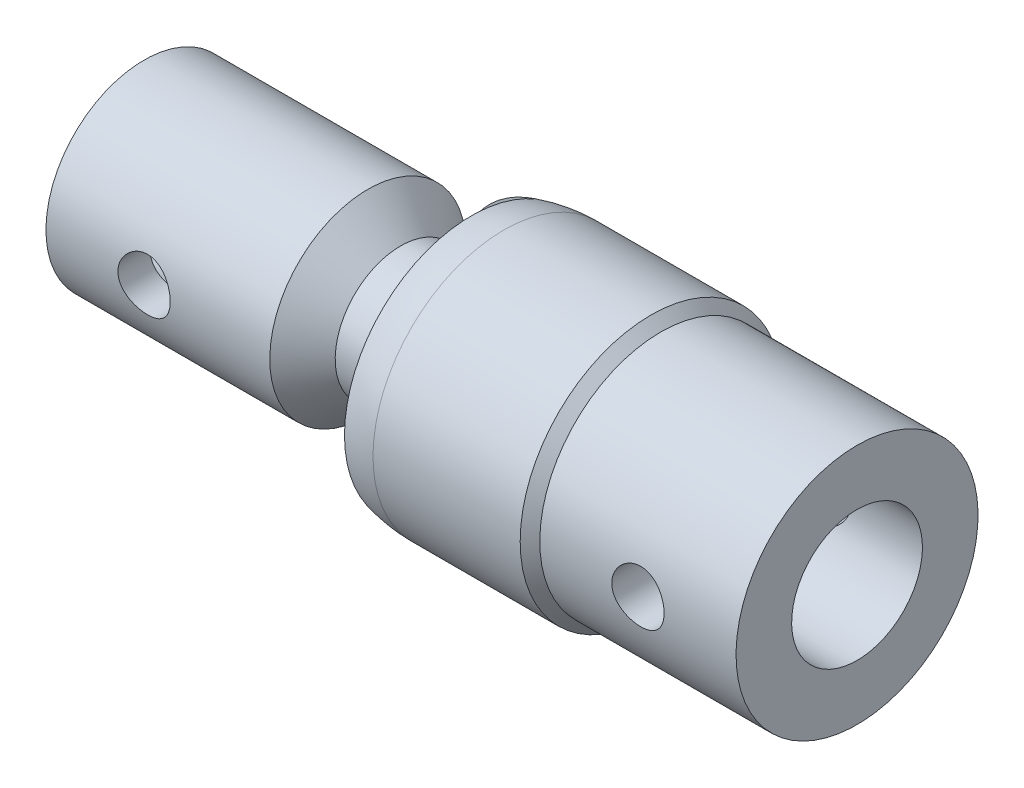
SolidWorks part; units mm, degrees
ref_plane "Front Plane" through (0, 0, 0) normal (0, 0, 1) x (1, 0, 0)
ref_plane "Top Plane" through (0, 0, 0) normal (0, 1, 0) x (1, 0, 0)
ref_plane "Right Plane" through (0, 0, 0) normal (1, 0, 0) x (0, 0, -1)
sketch "Sketch0" plane through (0, 0, 0) normal (0, 0, 1) x (1, 0, 0)
  line L0 (-43.6575, 0) -> (42.8625, 0) construction
  line L1 (42.8625, 7.9375) -> (19.05, 7.9375)
  line L2 (19.05, 7.9375) -> (19.05, -7.9375)
  line L3 (19.05, -7.9375) -> (42.8625, -7.9375)
  line L4 (42.8625, 14.6844) -> (42.8625, -14.6844) construction
  line L5 (-43.6575, 7.9375) -> (-19.845, 7.9375)
  line L6 (-19.845, 7.9375) -> (-19.845, -7.9375)
  line L7 (-19.845, -7.9375) -> (-43.6575, -7.9375)
  line L8 (-43.6575, 11.9062) -> (-43.6575, -11.9062) construction
  line L9 (0, 15.875) -> (0, -15.875) construction
  line L10 (0, 15.875) -> (0, -15.875) construction
  line L11 (42.8625, -14.6844) -> (19.05, -14.6844)
  line L12 (19.05, -14.6844) -> (17.8594, -15.875)
  line L13 (17.8594, -15.875) -> (0, -15.875)
  line L14 (-43.6575, -11.9062) -> (-16.4975, -11.9062)
  line L15 (-16.4975, -11.9062) -> (-12.5288, -7.9375)
  line L16 (-12.5288, -7.9375) -> (0, -7.9375)
  line L17 (5.6127, 5.6127) -> (11.2253, 11.2253) construction
  line L18 (-19.845, -7.9375) -> (-13.7482, -7.9375) construction
  circle A0 centre (0, 0) radius 15.875 construction
  circle A1 centre (0, 0) radius 7.9375 construction
  circle A2 centre (0, 0) radius 11.9062 construction
  point P5 (19.05, 0)
  point P30 (8.419, 8.419)
  dimension "D1" = 45
  dimension "F" = 43.6575
  dimension "G" = 42.8625
  dimension "A" = 15.875
  dimension "D2" = 45
  dimension "H" = 23.8125
  dimension "E" = 29.3687
  dimension "D" = 23.8125
  dimension "C" = 31.75
  dimension "D3" = 45
  dimension "D4" = 6.0969
  dimension "D5" = 7.3162
sketch "Sketch1" plane through (0, 0, 0) normal (0, 0, 1) x (1, 0, 0)
  line L0 (-12.5288, -7.9375) -> (0, -7.9375) construction
  line L1 (-16.4975, -11.9062) -> (-12.5288, -7.9375) construction
  line L2 (-43.6575, -11.9062) -> (-16.4975, -11.9062) construction
  line L3 (-19.845, -7.9375) -> (-43.6575, -7.9375) construction
  line L4 (-19.845, 7.9375) -> (-19.845, -7.9375) construction
  line L5 (-12.5288, -7.9375) -> (-8.8744, -7.9375)
  line L6 (-16.4975, -11.9062) -> (-12.5288, -7.9375)
  line L7 (-43.6575, -11.9062) -> (-16.4975, -11.9062)
  line L8 (-19.845, -7.9375) -> (-43.6575, -7.9375)
  line L9 (-19.845, 0) -> (-19.845, -7.9375)
  line L10 (-19.845, 0) -> (11.9062, 0) construction
  line L12 (-43.6575, -7.9375) -> (-43.6575, -11.9062)
  line L13 (-43.6575, 0) -> (42.8625, 0) construction
  line L14 (-19.845, 0) -> (11.9062, 0)
  arc A0 (-8.8744, -7.9375) -> (11.9062, 0) centre (0, 0) ccw
  circle A1 centre (0, 0) radius 11.9062 construction
revolve "Revolve1" add sketch "Sketch1" angle 360 about L10
sketch "Sketch2" plane through (0, 0, 0) normal (0, 0, 1) x (1, 0, 0)
  line L0 (19.05, 7.9375) -> (19.05, -7.9375) construction
  line L1 (19.05, -7.9375) -> (42.8625, -7.9375) construction
  line L2 (42.8625, -14.6844) -> (19.05, -14.6844) construction
  line L3 (19.05, -14.6844) -> (17.8594, -15.875) construction
  line L4 (17.8594, -15.875) -> (0, -15.875) construction
  line L5 (19.05, 0) -> (19.05, -7.9375)
  line L6 (19.05, -7.9375) -> (42.8625, -7.9375)
  line L7 (42.8625, -14.6844) -> (19.05, -14.6844)
  line L8 (19.05, -14.6844) -> (17.8594, -15.875)
  line L9 (17.8594, -15.875) -> (0, -15.875)
  line L10 (42.8625, -7.9375) -> (42.8625, -14.6844)
  line L11 (19.05, 0) -> (-15.875, 0) construction
  line L13 (-43.6575, 0) -> (42.8625, 0) construction
  line L14 (19.05, 0) -> (-15.875, 0)
  circle A0 centre (0, 0) radius 15.875 construction
  arc A1 (-15.875, 0) -> (0, -15.875) centre (0, 0) ccw
revolve "Revolve2" add sketch "Sketch2" angle 360 about L11
sketch "Sketch3" plane through (0, 0, 0) normal (0, 0, 1) x (1, 0, 0)
  line L0 (0, 0) -> (-7.9375, 0) construction
  line L1 (-43.6575, 0) -> (42.8625, 0) construction
  line L2 (-3.9688, 15.875) -> (-3.9687, -15.875)
  line L3 (-3.9688, 15.875) -> (-19.845, 15.875)
  line L4 (-3.9687, -15.875) -> (-19.845, -15.875)
  line L5 (-19.845, 15.875) -> (-19.845, -15.875)
  line L6 (-19.845, 7.9375) -> (-19.845, -7.9375) construction
  circle A0 centre (0, 0) radius 7.9375 construction
  point P9 (-3.9688, 0)
extrude "Cut-Extrude1" cut sketch "Sketch3" along normal through all and the other way blind 7.9375
sketch "Sketch5" plane through (0, 0, 0) normal (0, 0, 1) x (1, 0, 0)
  line L0 (-19.845, 7.9375) -> (-19.845, -7.9375) construction
  line L1 (-19.845, 6.8741) -> (-11.9062, 6.8741)
  line L2 (-19.845, 6.8741) -> (-19.845, -6.8741)
  line L3 (-19.845, -6.8741) -> (-11.9062, -6.8741)
  line L4 (-11.9062, 6.8741) -> (-11.9062, -6.8741)
  circle A0 centre (0, 0) radius 11.9062 construction
  arc A1 (-3.9688, 13.1629) -> (-3.9687, -13.1629) centre (0, 0) ccw construction
extrude "Cut-Extrude2" cut sketch "Sketch5" against normal through all
sketch "Sketch6" plane through (0, 0, 0) normal (0, 0, 1) x (1, 0, 0)
  line L0 (-12.1603, 0) -> (12.1603, 0) construction
  line L1 (-12.1603, 0) -> (12.1603, 0)
  circle A2 centre (0, 0) radius 12.1603
  arc A3 (-12.1603, 0) -> (12.1603, 0) centre (0, 0) ccw
  dimension "D1" = 0.254
revolve "Cut-Revolve2" cut sketch "Sketch6" angle 360 about L0
sketch "Sketch8" plane through (0, 0, 0) normal (0, 0, 1) x (1, 0, 0)
  line L0 (-43.6575, 0) -> (42.8625, 0) construction
  line L1 (-31.7513, 7.9375) -> (-31.7513, 0) construction
  line L2 (-43.6575, 7.9375) -> (-19.845, 7.9375) construction
  line L3 (30.9562, 7.9375) -> (30.9562, 0) construction
  line L4 (42.8625, 7.9375) -> (19.05, 7.9375) construction
  circle A0 centre (-31.7513, 0) radius 3.175
  circle A1 centre (30.9562, 0) radius 3.175
  dimension "D1" = 6.35
  dimension "D2" = 6.35
extrude "Cut-Extrude3" cut sketch "Sketch8" against normal through all and the other way through all
ref_axis "Axis1" through (0, 0, -17.4625) along (0, 0, 1)
move or copy body "Body-Move/Copy1" [suppressed] bodies to move or copy 106 copy no rotation origin (0, 0, 0) rotation axis (0, 0, -1) rotation angle 30
sketch "Sketch7" plane through (0, 0, 0) normal (0, 1, 0) x (1, 0, 0)
  line L0 (-43.6575, -7.9375) -> (-19.845, -7.9375)
  line L1 (-19.845, -7.9375) -> (-19.845, 7.9375)
  line L2 (-19.845, 7.9375) -> (-43.6575, 7.9375)
  line L3 (-43.6575, 7.9375) -> (-43.6575, -7.9375) construction
  line L4 (19.05, 7.9375) -> (19.05, -7.9375)
  line L5 (19.05, -7.9375) -> (42.8625, -7.9375)
  line L6 (19.05, 7.9375) -> (42.8625, 7.9375)
  point P2 (-19.845, 0)
  dimension "D1" = 15.875
equation "\"D5@Sketch0\" = \"D4@Sketch0\"*1.2"
equation "\"D2@Cut-Extrude1\" = \"A@Sketch0\"/2"
equation "\"D1@Sketch7\" = \"A@Sketch0\""
